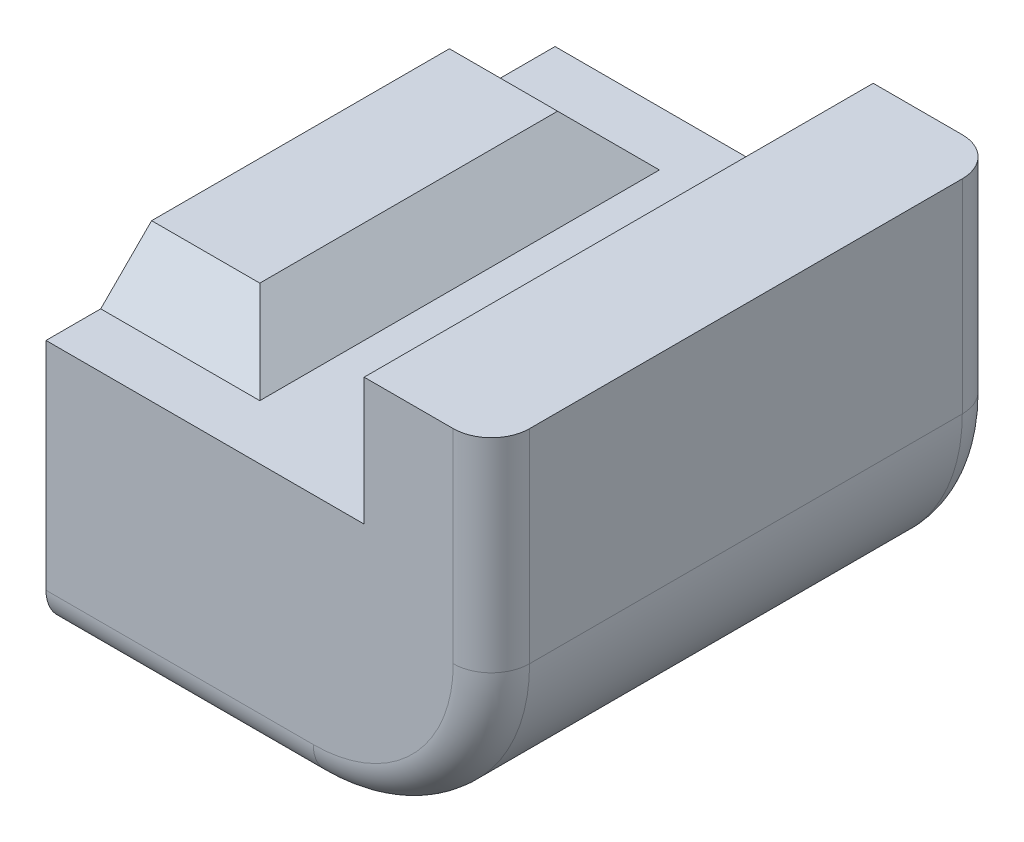
SolidWorks part; units mm, degrees
ref_plane "Front Plane" through (0, 0, 0) normal (0, 0, 1) x (1, 0, 0)
ref_plane "Top Plane" through (0, 0, 0) normal (0, 1, 0) x (1, 0, 0)
ref_plane "Right Plane" through (0, 0, 0) normal (1, 0, 0) x (0, 0, -1)
sketch "Sketch1" plane through (0, 0, 0) normal (0, 0, 1) x (1, 0, 0)
  line L1 (-175, -150) -> (175, -150)
  line L2 (-175, -150) -> (-175, 150)
  line L3 (-175, 150) -> (175, 150)
  line L4 (175, -150) -> (175, 150)
  line L5 (-175, -150) -> (175, 150) construction
  line L6 (-175, 150) -> (175, -150) construction
  point P0 (0, 0)
  dimension "D1" = 350
  dimension "D2" = 300
extrude "Boss-Extrude1" add sketch "Sketch1" along normal blind 117 and the other way blind 117
fillet "Fillet2" radius 140 1 edges at (175, -150, 0)
sketch "Sketch3" plane through (0, 0, 0) normal (0, 0, -1) x (-1, 0, 0)
  line L1 (-35, -150) -> (175, -150)
  line L2 (-175, -10) -> (-175, 150)
  line L3 (-175, 150) -> (175, 150)
  line L4 (175, -150) -> (175, 150)
  line L5 (-175, -150) -> (175, 150) construction
  line L6 (-175, 150) -> (175, -150) construction
  line L7 (175, 150) -> (-75, 150)
  line L8 (175, 150) -> (175, 50)
  line L9 (175, 50) -> (-75, 50)
  line L10 (-75, 150) -> (-75, 50)
  arc A0 (-35, -150) -> (-175, -10) centre (-35, -10) cw
  point P0 (0, 0)
  dimension "D1" = 140
  dimension "D2" = 250
  dimension "D3" = 100
extrude "Boss-Extrude2" add sketch "Sketch3" along normal blind 200 and the other way blind 200 contours L1 A0 L2 L3 L10 L9 L4 region at (8.5159, -26.3954, 0)
sketch "Sketch4" plane through (0, 0, -117) normal (0, 0, -1) x (-1, 0, 0)
  line L0 (175, 150) -> (175, 50) construction
  line L1 (175, 150) -> (-75, 150)
  line L2 (175, 150) -> (175, 90)
  line L3 (175, 90) -> (-75, 90)
  line L4 (-75, 150) -> (-75, 90)
  line L5 (-75, 150) -> (-75, 50) construction
  point P8 (0, 0)
  point P9 (0, 0)
  dimension "D1" = 60
extrude "Cut-Extrude1" cut sketch "Sketch4" against normal blind 540
sketch "Sketch6" plane through (0, 0, -117) normal (0, 0, -1) x (-1, 0, 0)
  line L0 (175, 50) -> (-75, 50) construction
  line L1 (-75, 90) -> (90, 90)
  line L2 (-75, 90) -> (-75, 50)
  line L3 (-75, 50) -> (90, 50)
  line L4 (90, 90) -> (90, 50)
  dimension "D1" = 165
extrude "Cut-Extrude2" cut sketch "Sketch6" against normal blind 540
fillet "Fillet4" radius 30 6 edges at (-70, -150, 200) (175, 70, 200) (-70, -150, -200) (175, 70, -200) (133.9949, -108.9949, 200) (133.9949, -108.9949, -200)
chamfer "Chamfer1" distance 40 angle 45 1 edges at (-90, 50, 0)
chamfer "Chamfer2" distance 40 angle 45 2 edges at (-112.5, 50, 117) (-112.5, 50, -117)
